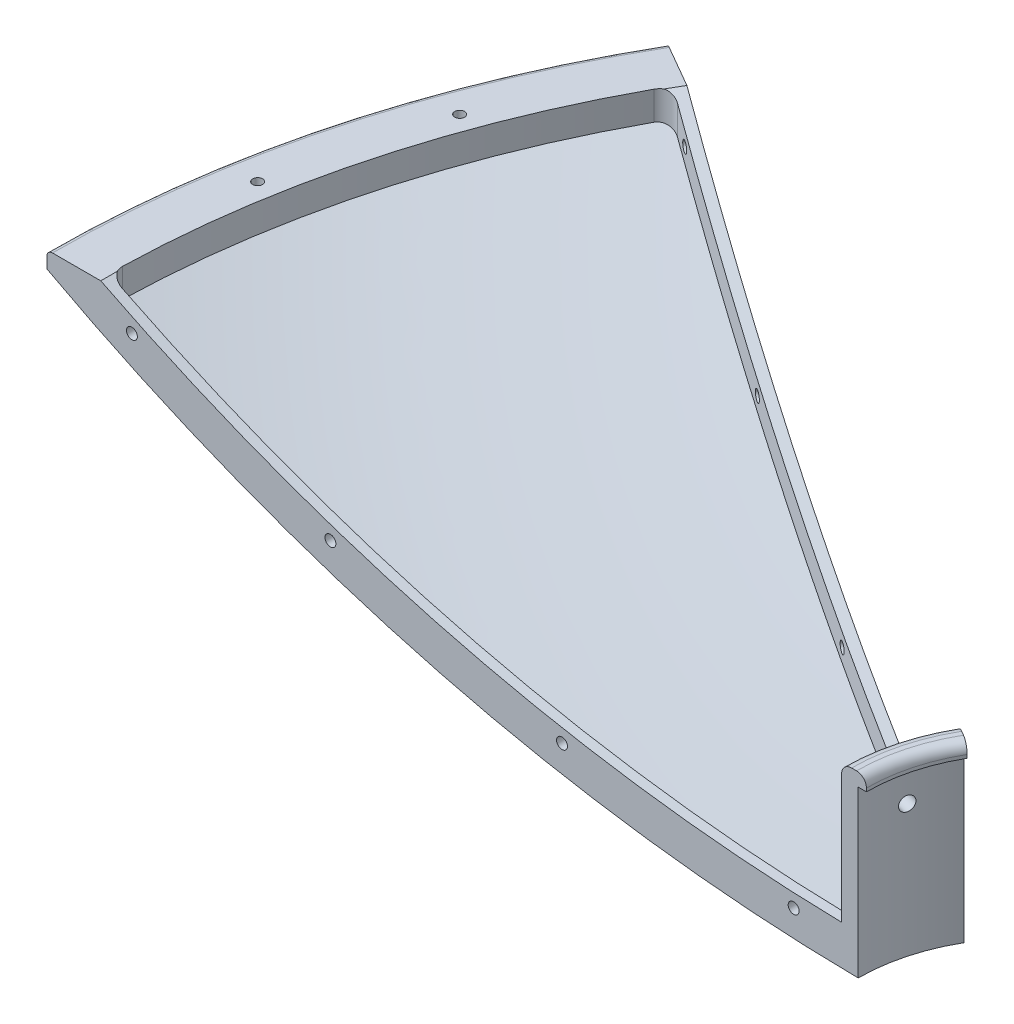
SolidWorks part; units mm, degrees
ref_plane "Front Plane" through (0, 0, 0) normal (0, 0, 1) x (1, 0, 0)
ref_plane "Top Plane" through (0, 0, 0) normal (0, 1, 0) x (1, 0, 0)
ref_plane "Right Plane" through (0, 0, 0) normal (1, 0, 0) x (0, 0, -1)
sketch "Sketch1" plane through (0, 0, 0) normal (0, 0, 1) x (1, 0, 0)
  line L0 (0, -150.7069) -> (-45, -150.7069) construction
  line L1 (-300, -82.3534) -> (-280, -82.3534) construction
  line L2 (-296, -87.5256) -> (-296, -63.1813) construction
  line L3 (0, -150.7069) -> (-45, -150.7069)
  line L4 (-294, -82.3534) -> (-280, -82.3534) construction
  line L5 (-296, -87.5256) -> (-296, -84.3534) construction
  line L6 (-295.7, -87.5256) -> (-295.7, -84.3534)
  line L7 (-294, -82.6534) -> (-280, -82.6534)
  line L8 (-295.7, -87.5256) -> (-295.7, -87.6867)
  line L9 (-280, -82.6534) -> (-280, -91.312)
  line L11 (-45, -146.7069) -> (0, -146.7069)
  line L12 (0, 0) -> (0, -150.7069) construction
  line L13 (0, -146.7069) -> (0, -150.7069)
  line L14 (0, 0) -> (0, -150.7069)
  arc A0 (-294, -82.3534) -> (-296, -84.3534) centre (-294, -84.3534) ccw construction
  arc A1 (-300, -85.3534) -> (-45, -150.7069) centre (-45, 379.457) ccw construction
  arc A2 (-294, -82.3534) -> (-296, -84.3534) centre (-294, -84.3534) ccw construction
  arc A3 (-295.7, -87.6867) -> (-45, -150.7069) centre (-45, 379.457) ccw
  arc A4 (-294, -82.6534) -> (-295.7, -84.3534) centre (-294, -84.3534) ccw
  arc A5 (-280, -91.312) -> (-45, -146.7069) centre (-45, 379.457) ccw
  arc A6 (-293.8085, -84.1622) -> (-45, -146.7069) centre (-45, 379.457) ccw construction
  dimension "D2" = 4
  dimension "D1" = 0.3
revolve "Revolve1" add sketch "Sketch1" angle 30 about L14 region at (-22.5, -147.6726, 0)
sketch "Sketch2" plane through (0, -82.6534, 0) normal (0, 1, 0) x (1, 0, 0)
  circle A0 centre (-281.655, 49.6634) radius 1.5 construction
  circle A1 centre (-268.7521, 97.8178) radius 1.5 construction
  circle A2 centre (-281.655, 49.6634) radius 1.5
  circle A3 centre (-268.7521, 97.8178) radius 1.5
extrude "Cut-Extrude1" cut sketch "Sketch2" against normal through all
ref_plane "Plane1" through (0, -100.7069, 0) normal (0, -1, 0) x (-1, 0, 0)
sketch "Sketch3" plane through (0, -150.7069, 0) normal (0, -1, 0) x (1, 0, 0)
  circle A0 centre (0, 0) radius 50.5
  dimension "D1" = 101
extrude "Cut-Extrude2" cut sketch "Sketch3" against normal through all
sketch "Sketch4" plane through (0, -100.7069, 0) normal (0, -1, 0) x (-1, 0, 0)
  line L0 (242.4871, 140) -> (43.7343, 25.25) construction
  line L1 (50.5, 0) -> (280, 0) construction
  line L2 (48.0644, 27.75) -> (43.7343, 25.25)
  line L3 (50.5, 0) -> (55.5, 0)
  arc A0 (50.5, 0) -> (43.7343, 25.25) centre (0, 0) ccw construction
  arc A1 (50.5, 0) -> (43.7343, 25.25) centre (0, 0) ccw
  arc A2 (55.5, 0) -> (48.0644, 27.75) centre (0, 0) ccw
  dimension "D1" = 5
extrude "Boss-Extrude1" add sketch "Sketch4" along normal up to next
sketch "Sketch5" plane through (0, 0, 0) normal (0.5, 0, -0.866) x (-0.866, 0, -0.5)
  line L0 (280, -82.6534) -> (279.4094, -82.6534)
  line L1 (280, -82.6534) -> (280, -91.312) construction
  line L2 (280, -82.6534) -> (280, -91.312) construction
  line L3 (55.5, -146.6021) -> (55.5, -138.6005) construction
  line L4 (55.5, -146.6021) -> (55.5, -100.7069) construction
  line L5 (55.5, -146.6021) -> (52.4747, -146.6021)
  line L6 (52.4747, -146.6021) -> (52.4747, -138.6005)
  line L7 (52.4747, -138.6005) -> (55.5, -138.6005)
  line L8 (280, -82.6534) -> (281.2843, -82.6534)
  line L9 (294, -82.6534) -> (280, -82.6534) construction
  line L10 (281.2843, -82.6534) -> (281.2843, -91.312)
  line L11 (281.2843, -91.312) -> (280, -91.312)
  arc A0 (276.427, -84.1542) -> (279.4094, -82.6534) centre (45, 379.457) ccw
  arc A1 (55.5, -146.6021) -> (280, -91.312) centre (45, 379.457) ccw construction
  arc A2 (55.3404, -138.6037) -> (276.427, -84.1542) centre (45, 379.457) ccw
  arc A3 (55.5, -138.6005) -> (276.427, -84.1542) centre (45, 379.457) ccw
  arc A4 (55.5, -146.6021) -> (280, -91.312) centre (45, 379.457) ccw
  dimension "D1" = 8
extrude "Boss-Extrude4" add sketch "Sketch5" against normal blind 3
ref_plane "Plane2" through (0, 0, 0) normal (0.2588, 0, -0.9659) x (-0.9659, 0, -0.2588)
sketch "Sketch6" plane through (0, 0, 0) normal (0.5, 0, -0.866) x (-0.866, 0, -0.5)
  line L0 (0, -1000) -> (0, 49000) construction
  circle A2 centre (70, -142.1081) radius 1.65
  arc A3 (55.5811, -142.5997) -> (281.2189, -86.2207) centre (45, 379.457) ccw
  arc A4 (55.5811, -142.5997) -> (281.2189, -86.2207) centre (45, 379.457) ccw construction
  circle A5 centre (140, -133.9922) radius 1.65
  circle A6 centre (210, -115.952) radius 1.65
  circle A7 centre (270, -91.7437) radius 1.65
  dimension "D2" = 3.3
  dimension "D3" = 70
  dimension "D4" = 140
  dimension "D5" = 210
  dimension "D6" = 270
  dimension "D1" = 4
extrude "Cut-Extrude4" cut sketch "Sketch6" against normal up to surface (3 mm away) up to face at (-142.8745, -118.742, -79.0245)
fillet "Fillet1" radius 4 1 edges at (-243.9732, -86.9827, -137.3939)
mirror "Mirror1" about plane through (0, 0, 0) normal (0.2588, 0, -0.9659) of "Boss-Extrude4", "Cut-Extrude4", "Fillet1"
ref_plane "Plane3" through (0, -85.6534, 0) normal (0, 1, 0) x (1, 0, 0)
sketch "Sketch8" plane through (0, -85.6534, 0) normal (0, 1, 0) x (1, 0, 0)
  circle A0 centre (-281.655, 49.6634) radius 1.5 construction
  circle A1 centre (-268.7521, 97.8178) radius 1.5 construction
  circle A2 centre (-281.655, 49.6634) radius 1.5 construction
  circle A3 centre (-268.7521, 97.8178) radius 1.5 construction
  circle A4 centre (-268.7521, 97.8178) radius 3.5
  circle A5 centre (-281.655, 49.6634) radius 3.5
  dimension "D1" = 7
  dimension "D2" = 7
extrude "Cut-Extrude5" cut sketch "Sketch8" against normal through all
ref_plane "Plane4" through (-53.6089, 0, -14.3645) normal (-0.9659, 0, -0.2588) x (-0.2588, 0, 0.9659)
sketch "Sketch9" plane through (-53.6089, 0, -14.3645) normal (-0.9659, 0, -0.2588) x (-0.2588, 0, 0.9659)
  line L2 (14.3645, -100.7069) -> (-14.3645, -100.7069) construction
  line L3 (0, 37.4137) -> (0, -37.4137) construction
  circle A0 centre (0, -110.7069) radius 2.15
  point P2 (0, 0)
  point P3 (0, 0)
  dimension "D1" = 4.3
  dimension "D2" = 10
extrude "Cut-Extrude6" cut sketch "Sketch9" against normal through all
sketch "Sketch10" plane through (0, -100.7069, 0) normal (0, 1, 0) x (1, 0, 0)
  line L0 (-48.0644, 27.75) -> (-41.5692, 24)
  line L1 (-55.5, 0) -> (-48, 0)
  line L2 (-48.0644, 27.75) -> (-43.7343, 25.25) construction
  line L3 (-50.5, 0) -> (-55.5, 0) construction
  arc A0 (-41.5692, 24) -> (-48, 0) centre (0, 0) ccw
  arc A1 (-55.5, 0) -> (-48.0644, 27.75) centre (0, 0) cw
  point P13 (0, 0)
  dimension "D1" = 96
extrude "Boss-Extrude5" add sketch "Sketch10" along normal blind 4
fillet "Fillet2" radius 3 2 edges at (-46.3644, -96.7069, -12.4233) (-53.6089, -96.7069, -14.3645)
